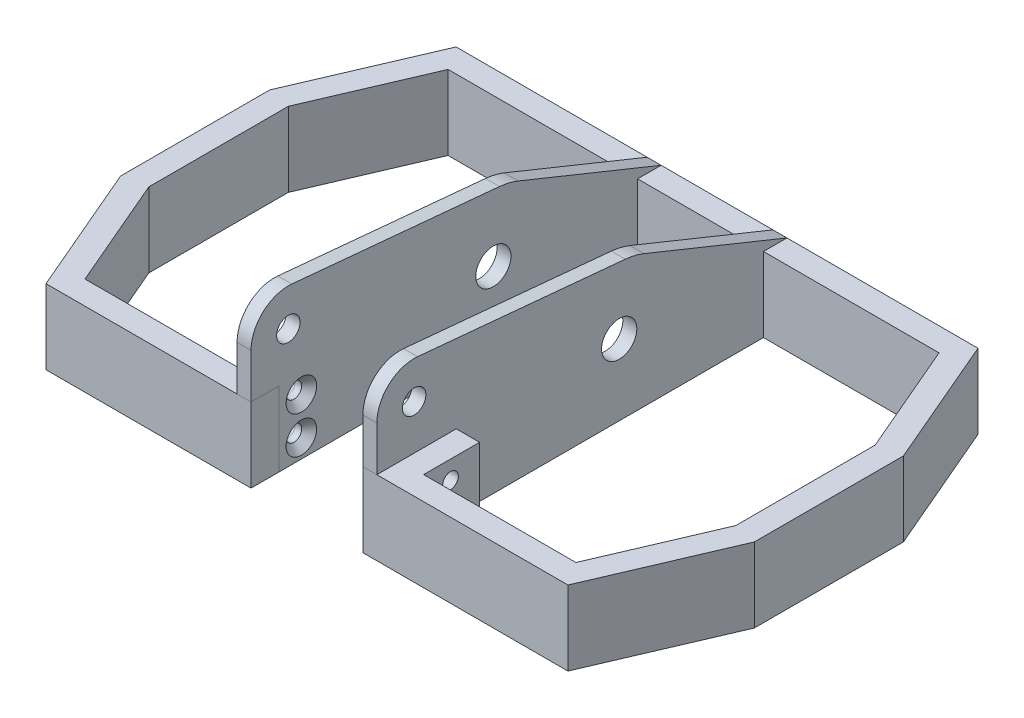
SolidWorks part; units mm, degrees
ref_plane "Front Plane" through (0, 0, 0) normal (0, 0, 1) x (1, 0, 0)
ref_plane "Top Plane" through (0, 0, 0) normal (0, 1, 0) x (1, 0, 0)
ref_plane "Right Plane" through (0, 0, 0) normal (1, 0, 0) x (0, 0, -1)
sketch "Sketch1" plane through (0, 0, 0) normal (1, 0, 0) x (0, 0, -1)
  line L0 (-12.7, 0) -> (-12.7, -40.64)
  line L1 (-12.7, -40.64) -> (127, -40.64)
  line L3 (1.1829, 12.6448) -> (71.9538, 6.0243)
  line L4 (78.3285, 4.4708) -> (127, -15.24)
  line L6 (127, -15.24) -> (127, -40.64)
  circle A0 centre (0, 0) radius 40.64 construction
  circle A1 centre (0, 0) radius 4
  circle A2 centre (0, 0) radius 12.7
  circle A3 centre (69.85, -16.465) radius 21 construction
  circle A4 centre (69.85, -16.465) radius 6
  arc A5 (71.9538, 6.0243) -> (78.3285, 4.4708) centre (69.85, -16.465) cw
  point P11 (69.85, -37.465)
  dimension "D1" = 81.28
  dimension "D2" = 8
  dimension "D3" = 25.4
  dimension "D4" = 42
  dimension "D8" = 12
  dimension "D9" = 25.4
  dimension "D11" = 1.5875
  dimension "D5" = 3.175
  dimension "D6" = 69.85
  dimension "D10" = 139.7
extrude "Boss-Extrude1" add sketch "Sketch1" along normal blind 4.7625 from offset 19.05 contours A2 L0 L1 L4 A4 | A2 A1 region at (0, -19.1617, -54.8752) region at (0, 9.1236, 8.3099)
mirror "Mirror2" about plane through (0, 0, 0) normal (1, 0, 0) of bodies 101
sketch "Sketch2" plane through (0, -40.64, 0) normal (0, -1, 0) x (1, 0, 0)
  line L0 (19.05, 12.7) -> (88.9, 12.7)
  line L1 (88.9, 12.7) -> (107.95, -31.75)
  line L2 (107.95, -31.75) -> (107.95, -82.55)
  line L3 (107.95, -82.55) -> (88.9, -127)
  line L4 (88.9, -127) -> (-88.9, -127)
  line L6 (0, -127) -> (0, 0) construction
  line L7 (-19.05, 12.7) -> (-88.9, 12.7)
  line L8 (-88.9, 12.7) -> (-107.95, -31.75)
  line L9 (-107.95, -31.75) -> (-107.95, -82.55)
  line L10 (-107.95, -82.55) -> (-88.9, -127)
  point P13 (0, 0)
  point P14 (19.05, 12.7)
  dimension "D1" = 69.85
  dimension "D2" = 19.05
  dimension "D3" = 44.45
extrude "Extrude-Thin1" add sketch "Sketch2" against normal blind 25.4 separate body thin thin type one direction reverse wall 8
sketch "Sketch3" plane through (19.05, 0, 0) normal (-1, 0, 0) x (0, 0, 1)
  line L0 (-127, -15.24) -> (-119, -15.24)
  line L1 (-119, -15.24) -> (-119, -27.94)
  line L2 (-119, -27.94) -> (-127, -27.94)
  line L3 (-127, -15.24) -> (-127, -40.64) construction
  point P8 (-119, -26.1311)
extrude "Cut-Extrude1" cut sketch "Sketch3" against normal through all both and the other way through all flip side to cut
sketch "Sketch4" plane through (0, 0, -127) normal (0, 0, -1) x (-1, 0, 0)
  line L4 (23.8125, -27.94) -> (19.05, -27.94)
  line L5 (19.05, -27.94) -> (19.05, -40.64)
  line L6 (19.05, -40.64) -> (23.8125, -40.64)
  line L7 (23.8125, -40.64) -> (23.8125, -27.94)
  line L8 (23.8125, -27.94) -> (19.05, -27.94)
  line L9 (19.05, -27.94) -> (19.05, -40.64)
  line L10 (19.05, -40.64) -> (23.8125, -40.64)
  line L11 (23.8125, -40.64) -> (23.8125, -27.94)
  line L12 (-19.05, -27.94) -> (-23.8125, -27.94)
  line L13 (-23.8125, -27.94) -> (-23.8125, -40.64)
  line L14 (-23.8125, -40.64) -> (-19.05, -40.64)
  line L15 (-19.05, -40.64) -> (-19.05, -27.94)
  line L16 (-19.05, -27.94) -> (-23.8125, -27.94)
  line L17 (-23.8125, -27.94) -> (-23.8125, -40.64)
  line L18 (-23.8125, -40.64) -> (-19.05, -40.64)
  line L19 (-19.05, -40.64) -> (-19.05, -27.94)
  dimension "D1" = 0
  dimension "D2" = 0
extrude "Cut-Extrude2" cut sketch "Sketch4" against normal blind 20.32
sketch "Sketch5" plane through (0, -40.64, 0) normal (0, -1, 0) x (1, 0, 0)
  line L0 (-31.75, 4.7) -> (-31.75, -14.35)
  line L1 (-19.05, 4.7) -> (-83.6248, 4.7) construction
  line L3 (-31.75, -14.35) -> (-19.05, -14.35)
  line L4 (-19.05, 12.7) -> (-19.05, -127) construction
  line L5 (-19.05, -14.35) -> (-19.05, 4.7)
  line L6 (-19.05, 4.7) -> (-31.75, 4.7)
  line L7 (0, 0) -> (0, -28.6389) construction
  line L8 (19.05, -14.35) -> (19.05, 4.7)
  line L9 (19.05, 4.7) -> (31.75, 4.7)
  line L10 (31.75, 4.7) -> (31.75, -14.35)
  line L11 (31.75, -14.35) -> (19.05, -14.35)
  point P4 (-39.05, -11.3)
  point P18 (0, 0)
  dimension "D1" = 19.05
  dimension "D2" = 12.7
extrude "Boss-Extrude2" add sketch "Sketch5" against normal up to surface (25.4 mm away) up to face at (0, -15.24, -43.98)
sketch "Sketch9" plane through (-19.05, 0, 0) normal (1, 0, 0) x (0, 0, -1)
  line L0 (-12.7, -15.24) -> (14.35, -15.24) construction
  line L1 (-12.7, -40.64) -> (-3.175, -40.64)
  line L2 (-12.7, -40.64) -> (-12.7, -15.24)
  line L3 (-12.7, -15.24) -> (-3.175, -15.24)
  line L4 (-3.175, -40.64) -> (-3.175, -15.24)
  point P4 (0, 0)
  point P8 (0, 0)
  dimension "D1" = 9.525
extrude "Cut-Extrude6" cut sketch "Sketch9" against normal up to surface (4.7625 mm away) and the other way up to surface (42.8625 mm away) up to face at (-23.8125, -14.1201, -74.2329) other way up to face at (23.8125, -14.1201, -74.2329)
sketch "Sketch10" plane through (-19.05, 0, 0) normal (1, 0, 0) x (0, 0, -1)
  line L1 (-3.175, -40.64) -> (14.35, -40.64)
  line L2 (-3.175, -40.64) -> (-3.175, -15.24)
  line L3 (-3.175, -15.24) -> (14.35, -15.24)
  line L4 (14.35, -40.64) -> (14.35, -15.24)
extrude "Cut-Extrude7" cut sketch "Sketch10" against normal up to surface (4.7625 mm away) and the other way up to surface (42.8625 mm away) up to face at (-23.8125, -14.3067, -61.3316) other way up to face at (23.8125, -14.3067, -61.3316)
sketch "Sketch11" plane through (19.05, 0, 0) normal (-1, 0, 0) x (0, 0, 1)
  line L3 (3.175, -15.24) -> (3.175, -40.64) construction
  line L4 (12.7, -15.24) -> (-31.75, -15.24) construction
  line L5 (12.7, -40.64) -> (-31.75, -40.64) construction
  circle A0 centre (-4.445, -34.29) radius 2.667
  circle A1 centre (-4.445, -21.59) radius 2.667
  point P7 (0, 0)
  point P8 (0, 0)
  point P11 (0, 0)
  dimension "D1" = 7.62
  dimension "D3" = 6.35
  dimension "D4" = 5.334
  dimension "D2" = 6.35
extrude "Cut-Extrude8" cut sketch "Sketch11" against normal blind 20.32 and the other way blind 58.42
chamfer "Chamfer1" distance 2.54 angle 45 2 edges at (19.05, -34.29, -7.112) (19.05, -21.59, -7.112)
chamfer "Chamfer2" distance 2.54 angle 45 2 edges at (-19.05, -21.59, -1.778) (-19.05, -34.29, -1.778)
